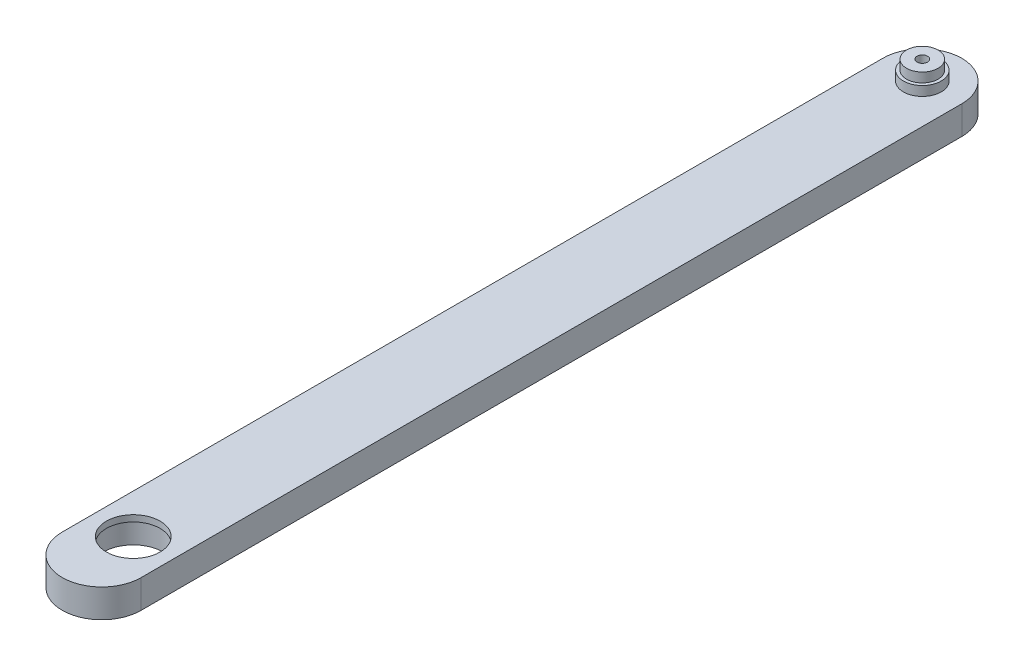
SolidWorks part; units mm, degrees
material "7075-T6 (SN)"
ref_plane "정면" through (0, 0, 0) normal (0, 0, 1) x (1, 0, 0)
ref_plane "윗면" through (0, 0, 0) normal (0, 1, 0) x (1, 0, 0)
ref_plane "우측면" through (0, 0, 0) normal (1, 0, 0) x (0, 0, -1)
sketch "스케치1" plane through (0, 0, 0) normal (0, 1, 0) x (1, 0, 0)
  circle A0 centre (0, 0) radius 5
  dimension "D1" = 10
extrude "보스-돌출1" add sketch "스케치1" along normal blind 10.5 and the other way blind 10.5
sketch "스케치6" plane through (0, 0, 0) normal (0, 1, 0) x (1, 0, 0)
  line L0 (-12.5, 0) -> (-12.5, -260)
  line L1 (0, 0) -> (0, -260) construction
  line L2 (12.5, 0) -> (12.5, -260)
  arc A0 (12.5, 0) -> (-12.5, 0) centre (0, 0) ccw
  arc A1 (-12.5, -260) -> (12.5, -260) centre (0, -260) ccw
  dimension "D1" = 25
  dimension "D3" = 25
  dimension "D2" = 260
extrude "보스-돌출3" add sketch "스케치6" along normal blind 4.5 and the other way blind 4.5
sketch "스케치7" plane through (0, -4.5, 0) normal (0, -1, 0) x (1, 0, 0)
  circle A0 centre (0, 0) radius 6
  dimension "D1" = 12
extrude "보스-돌출4" add sketch "스케치7" along normal blind 3
sketch "스케치8" plane through (0, 4.5, 0) normal (0, 1, 0) x (1, 0, 0)
  circle A0 centre (0, 0) radius 6
  dimension "D1" = 12
extrude "보스-돌출5" add sketch "스케치8" along normal blind 3
sketch "스케치9" plane through (0, -4.5, 0) normal (0, -1, 0) x (1, 0, 0)
  circle A0 centre (0, 250) radius 9.5
  dimension "D1" = 19
  dimension "D2" = 250
extrude "컷-돌출1" cut sketch "스케치9" against normal blind 7
sketch "스케치10" plane through (0, 2.5, 0) normal (0, -1, 0) x (1, 0, 0)
  circle A0 centre (0, 250) radius 8.5
  dimension "D1" = 17
  dimension "D2" = 250
extrude "컷-돌출2" cut sketch "스케치10" against normal through all
hole_wizard "M4 탭을 위한 탭 드릴1" positions "스케치21" profile "스케치17" hole size "M4" standard "ISO" end condition through all
sketch "스케치21" plane through (0, -10.5, 0) normal (0, -1, 0) x (-1, 0, 0)
  point P0 (0, 0)
sketch "스케치17" plane through (0, -10.5, 0) normal (1, 0, 0) x (0, 0, -1)
  line L0 (0, 0) -> (0, 21)
  line L1 (0, 21) -> (1.65, 21)
  line L2 (1.65, 21) -> (1.65, 0)
  line L5 (1.65, 0) -> (0, 0)
  line L11 (0, -6.35) -> (0, 107.95) construction
  dimension "관통 구멍 지름" = 3.3
  dimension "관통 구멍 깊이" = 21
